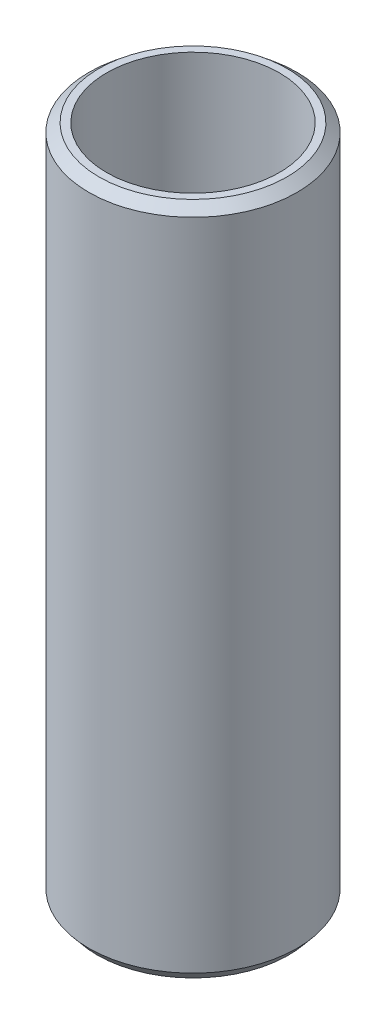
SolidWorks part; units mm, degrees
ref_plane "Front Plane" through (0, 0, 0) normal (0, 0, 1) x (1, 0, 0)
ref_plane "Top Plane" through (0, 0, 0) normal (0, 1, 0) x (1, 0, 0)
ref_plane "Right Plane" through (0, 0, 0) normal (1, 0, 0) x (0, 0, -1)
sketch "Sketch1" plane through (0, 0, 0) normal (0, 1, 0) x (1, 0, 0)
  circle A0 centre (0, 0) radius 50
  dimension "SHAFT_OD" = 100
extrude "Boss-Extrude1" add sketch "Sketch1" along normal blind 323.3554
sketch "Sketch2" plane through (0, 0, 0) normal (0, 1, 0) x (1, 0, 0)
  circle A0 centre (0, 0) radius 41.5183
  dimension "BORE_D" = 83.0366
extrude "Cut-Extrude1" cut sketch "Sketch2" along normal through all
chamfer "Chamfer1" distance 4.0207 angle 50.257 2 edges at (0, 323.3554, 50) (0, 0, 50) first distance on face at (0, 323.3554, 50) first distance on face at (0, 0, 41.5183)
